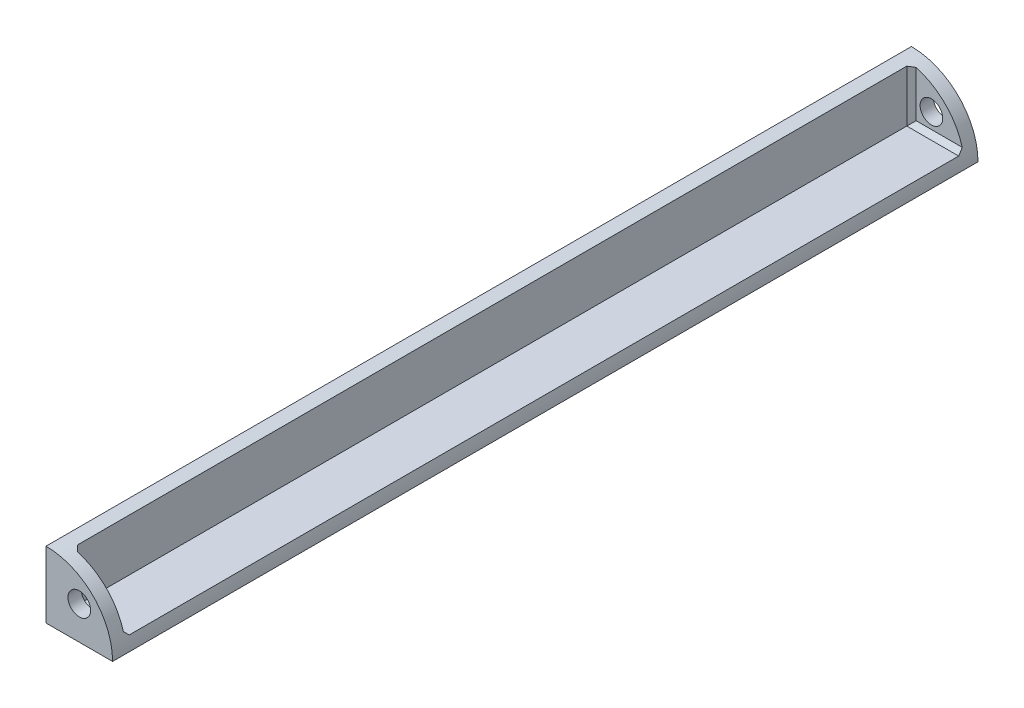
SolidWorks part; units mm, degrees
ref_plane "Front Plane" through (0, 0, 0) normal (0, 0, 1) x (1, 0, 0)
ref_plane "Top Plane" through (0, 0, 0) normal (0, 1, 0) x (1, 0, 0)
ref_plane "Right Plane" through (0, 0, 0) normal (1, 0, 0) x (0, 0, -1)
sketch "Sketch1" plane through (0, 0, 0) normal (0, 0, 1) x (1, 0, 0)
  line L0 (0, 0) -> (0, 10)
  line L1 (0, 0) -> (10, 0)
  arc A0 (10, 0) -> (0, 10) centre (0, 0) ccw
  circle A1 centre (5, 5) radius 1.7
  dimension "D1" = 20
  dimension "D2" = 3.4
  dimension "D3" = 5
  dimension "D4" = 5
extrude "Boss-Extrude1" add sketch "Sketch1" along normal blind 2
sketch "Sketch2" plane through (0, 0, 2) normal (0, 0, 1) x (1, 0, 0)
  line L0 (0, 0) -> (2, 0)
  line L1 (0, 0) -> (10, 0) construction
  line L2 (2, 0) -> (2, 9.798)
  line L3 (0, 0) -> (0, 2)
  line L4 (0, 10) -> (0, 0) construction
  line L5 (0, 2) -> (9.798, 2)
  line L6 (0, 10) -> (0, 2)
  line L7 (10, 0) -> (2, 0)
  arc A0 (0, 10) -> (10, 0) centre (0, 0) cw
  line M3 (0, 0) -> (10, 0)
  arc M4 (10, 0) -> (0, 10) centre (0, 0) ccw
  line M5 (0, 10) -> (0, 0)
  dimension "D1" = 2
  dimension "D2" = 2
extrude "Boss-Extrude2" add sketch "Sketch2" along normal blind 126 contours L5 L2 M5 M3 | L5 L2 M5 M4 | L5 L2 M3 M4 region at (1, 1, 2) region at (5.9667, 0.9958, 2) region at (0.9958, 5.9667, 2)
sketch "Sketch3" plane through (0, 0, 128) normal (0, 0, 1) x (1, 0, 0)
  line L0 (0, 0) -> (10, 0) construction
  line L1 (0, 10) -> (0, 0) construction
  arc A0 (0, 10) -> (10, 0) centre (0, 0) cw
  circle A1 centre (5, 5) radius 1.7
  line M1 (9.798, 2) -> (2, 2)
  line M2 (2, 2) -> (2, 9.798)
  arc M3 (2, 9.798) -> (0, 10) centre (0, 0) ccw
  line M4 (0, 10) -> (0, 0)
  line M5 (0, 0) -> (10, 0)
  arc M6 (10, 0) -> (9.798, 2) centre (0, 0) ccw
  dimension "D1" = 10
  dimension "D2" = 3.4
  dimension "D3" = 5
  dimension "D4" = 5
extrude "Boss-Extrude3" add sketch "Sketch3" along normal blind 2 contours A0 A1 M2 M1 | M6 M1 M2 M3 M4 M5 region at (0.9909, 9.8087, 128) region at (6.9931, 6.9931, 128)
chamfer "Chamfer1" distance 0.7 angle 45 4 edges at (2, 5.899, 2) (5.899, 2, 2) (5.899, 2, 128) (2, 5.899, 128)
